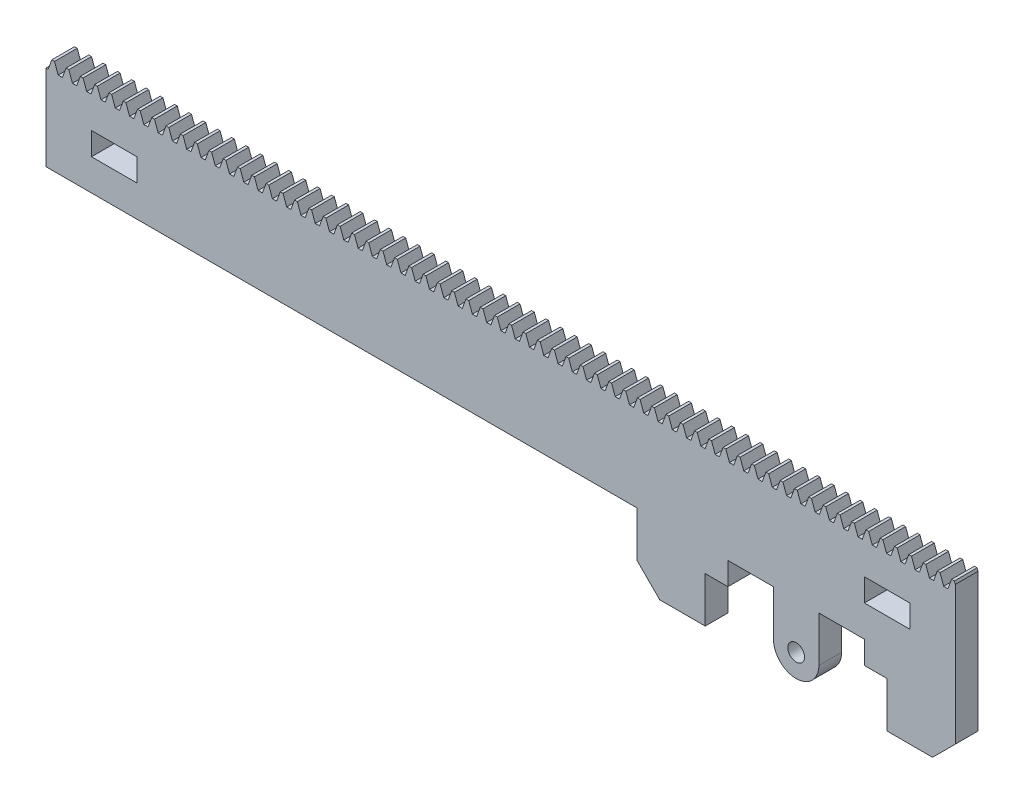
SolidWorks part; units mm, degrees
extrude "Blank" add sketch "BlankSke" against normal blind 6.35
sketch "BlankSke" plane through (0, 0, 0) normal (0, 0, 1) x (1, 0, 0)
  line L1 (0, 0) -> (254, 0)
  line L2 (0, 0) -> (0, 26.67)
  line L3 (0, 26.67) -> (254, 26.67)
  line L4 (254, 0) -> (254, 26.67)
  dimension "Length" = 254
ref_plane "Plane1" through (0, 0, 0) normal (0, 0, 1) x (1, 0, 0)
ref_plane "Plane2" through (0, 0, 0) normal (0, 1, 0) x (1, 0, 0)
ref_plane "Plane3" through (0, 0, 0) normal (1, 0, 0) x (0, 0, -1)
sketch "HoldingSke" plane through (0, 0, 0) normal (0, 1, 0) x (1, 0, 0)
  line L0 (0, 0) -> (389.1506, -326.5361)
  line L1 (-15, 0) -> (100, 0) construction
  line L2 (0, 0) -> (-2.1039, 2.3779)
  line L3 (0, 0) -> (-11.863, 4.5341)
  line L4 (0, 0) -> (3.6497, 7.8269)
  line L5 (0, 0) -> (-23.7986, -8.8762)
  line L6 (0, 0) -> (-10.5278, -7.1032)
  line L9 (-71.009, 38.7566) -> (167.673, 125.6297)
  line L10 (-76.2, 71.12) -> (-50.8, 71.12)
  line L11 (0, 0) -> (-6.35, 0)
  line L12 (-76.2, 101.6) -> (-76.1492, 101.6)
  line L13 (24.9733, 27.94) -> (52.9518, 28.4284)
  line L14 (24.9733, 27.94) -> (25.0241, 27.9398)
  line L15 (24.9733, 27.94) -> (100.4021, 29.52)
  circle A0 centre (0, 0) radius 19.05
  circle A1 centre (0, 0) radius 12.7
  circle A2 centre (0, 0) radius 12.7
  dimension "Num_teeth" = 65
  dimension "Width" = 6.35
  dimension "Length" = 254
  dimension "Pitch_height" = 25.4
sketch "TooCutSkeIll" plane through (0, 0, 0) normal (0, 0, 1) x (1, 0, 0)
  line L0 (-1.5999, 26.6366) -> (-0.6682, 24.0766)
  line L1 (-0.3817, 23.876) -> (0.3817, 23.876)
  line L2 (0.6682, 24.0766) -> (1.5999, 26.6366)
  line L3 (254, 26.67) -> (0, 26.67) construction
  line L4 (0, 0) -> (0, 64.897) construction
  line L5 (-13.208, 25.4) -> (12.954, 25.4) construction
  line L6 (0, 0) -> (254, 0) construction
  line L7 (1.1499, 25.4) -> (1.1499, 48.7463) construction
  line L8 (-1.1499, 25.4) -> (-1.1499, 48.7463) construction
  line L9 (1.6477, 26.67) -> (1.6477, 26.6954)
  line L10 (-1.6477, 26.67) -> (-1.6477, 26.6954)
  line L11 (-1.6477, 26.6954) -> (1.6477, 26.6954)
  arc A0 (0.3817, 23.876) -> (0.6682, 24.0766) centre (0.3817, 24.1808) ccw
  arc A1 (-0.6682, 24.0766) -> (-0.3817, 23.876) centre (-0.3817, 24.1808) ccw
  arc A2 (1.6477, 26.67) -> (1.5999, 26.6366) centre (1.6477, 26.6192) ccw
  arc A3 (-1.5999, 26.6366) -> (-1.6477, 26.67) centre (-1.6477, 26.6192) ccw
  dimension "Addendum_plus" = 1.2954
  dimension "Pitch_height" = 25.4
  dimension "Pressure_angle" = 20
  dimension "Gap_width" = 2.2997
  dimension "Dedendum" = 1.524
extrude "ToothCutIll" [suppressed] cut sketch "TooCutSkeIll" against normal through all
sketch "TooCutSkeSim" plane through (0, 0, 0) normal (0, 0, 1) x (1, 0, 0)
  line L0 (0.5952, 23.876) -> (-0.5952, 23.876)
  line L1 (1.6213, 26.6954) -> (0.5952, 23.876)
  line L2 (0, 17.4625) -> (0, 53.467) construction
  line L3 (1.6213, 26.6954) -> (-1.6213, 26.6954)
  line L6 (-1.6213, 26.6954) -> (-0.5952, 23.876)
  line L9 (-1.1499, 25.4) -> (1.1499, 25.4) construction
  line L10 (0, 0) -> (254, 0) construction
  line L11 (1.1499, 25.4) -> (1.1499, 53.467) construction
  line L12 (-1.1499, 25.4) -> (-1.1499, 53.467) construction
  dimension "Addendum_plus" = 1.2954
  dimension "Pitch_height" = 25.4
  dimension "Pressure_angle" = 20
  dimension "Gap_width" = 2.2997
  dimension "Dedendum" = 1.524
extrude "ToothCutSim" cut sketch "TooCutSkeSim" against normal through all
pattern_linear "TeethCuts" count 65 spacing 3.9898 along (1, 0, 0) of "ToothCutIll", "ToothCutSim"
sketch "Sketch3" plane through (0, 0, 0) normal (0, 0, 1) x (1, 0, 0)
  line L0 (0, 0) -> (254, 0) construction
  line L1 (234.95, 0) -> (254, 0)
  line L2 (234.95, -6.35) -> (234.95, -19.05)
  line L3 (234.95, -19.05) -> (254, -19.05)
  line L4 (254, 0) -> (254, -19.05)
  line L5 (254, 0) -> (254, 25.9462) construction
  line L6 (209.55, -6.35) -> (209.55, 0) construction
  line L7 (234.95, -6.35) -> (228.6, -6.35)
  line L8 (215.9, 0) -> (203.2, 0)
  line L9 (234.95, 0) -> (228.6, 0)
  line L10 (228.6, -6.35) -> (228.6, 0)
  line L11 (215.9, 0) -> (215.9, -6.35)
  line L12 (215.9, -6.35) -> (203.2, -6.35)
  line L13 (203.2, 0) -> (203.2, -6.35)
  line L14 (190.5, -6.35) -> (190.5, 0)
  line L15 (184.15, 0) -> (190.5, 0)
  line L16 (184.15, -6.35) -> (190.5, -6.35)
  line L17 (165.1, 0) -> (165.1, -19.05)
  line L18 (184.15, -19.05) -> (165.1, -19.05)
  line L19 (184.15, -6.35) -> (184.15, -19.05)
  line L20 (184.15, 0) -> (165.1, 0)
  dimension "D1" = 19.05
  dimension "D2" = 0
  dimension "D3" = 19.05
  dimension "D4" = 6.35
  dimension "D5" = 6.35
  dimension "D6" = 6.35
  dimension "D7" = 12.7
  dimension "D8" = 12.7
extrude "Boss-Extrude2" add sketch "Sketch3" against normal up to surface (6.35 mm away) up to face at (127.1733, 25.0804, -6.35)
sketch "Sketch4" plane through (0, 0, 0) normal (0, 0, 1) x (1, 0, 0)
  line L0 (209.55, -6.35) -> (209.55, -12.5878) construction
  line L1 (203.2, -6.35) -> (215.9, -6.35) construction
  line L2 (215.9, 0) -> (228.6, 0) construction
  line L3 (215.9, -12.7) -> (215.9, -6.35)
  line L4 (215.9, -6.35) -> (203.2, -6.35)
  line L5 (203.2, -6.35) -> (203.2, -12.7)
  circle A0 centre (209.55, -12.7) radius 2.3495
  arc A1 (203.2, -12.7) -> (215.9, -12.7) centre (209.55, -12.7) ccw
  dimension "D1" = 4.699
  dimension "D2" = 12.7
extrude "Boss-Extrude3" add sketch "Sketch4" against normal up to surface (6.35 mm away) up to face at (130.7232, 23.3872, -6.35)
chamfer "Chamfer1" distance 6.35 angle 45 2 edges at (165.1, -19.05, -3.175) (254, -19.05, -3.175)
sketch "Sketch6" plane through (0, 0, -6.35) normal (0, 0, -1) x (-1, 0, 0)
  line L0 (0, 11.938) -> (-254, 11.938) construction
  line L1 (0, 23.876) -> (0, 0) construction
  line L2 (-254, -12.7) -> (-254, 25.9462) construction
  line L4 (-25.4, 8.763) -> (-12.7, 8.763)
  line L5 (-25.4, 8.763) -> (-25.4, 15.113)
  line L6 (-25.4, 15.113) -> (-12.7, 15.113)
  line L7 (-12.7, 8.763) -> (-12.7, 15.113)
  line L8 (-25.4, 8.763) -> (-12.7, 15.113) construction
  line L9 (-25.4, 15.113) -> (-12.7, 8.763) construction
  point P6 (-19.05, 11.938)
  dimension "D1" = 12.7
  dimension "D2" = 6.35
  dimension "D3" = 12.7
extrude "Cut-Extrude2" cut sketch "Sketch6" against normal through all
sketch "Sketch8" plane through (0, 0, -6.35) normal (0, 0, -1) x (-1, 0, 0)
  line L0 (0, 11.938) -> (-254, 11.938) construction
  line L1 (0, 23.876) -> (0, 0) construction
  line L2 (-254, -12.7) -> (-254, 25.9462) construction
  line L4 (-228.6, 8.763) -> (-241.3, 8.763)
  line L5 (-228.6, 8.763) -> (-228.6, 15.113)
  line L6 (-228.6, 15.113) -> (-241.3, 15.113)
  line L7 (-241.3, 8.763) -> (-241.3, 15.113)
  line L8 (-228.6, 8.763) -> (-241.3, 15.113) construction
  line L9 (-228.6, 15.113) -> (-241.3, 8.763) construction
  point P6 (-234.95, 11.938)
  dimension "D1" = 12.7
  dimension "D2" = 6.35
  dimension "D3" = 12.7
extrude "Cut-Extrude3" cut sketch "Sketch8" against normal through all
equation "' \"Pitch@HoldingSke\" = 4"
equation "' \"Num_teeth@HoldingSke\" = 12"
equation "' \"Ap@HoldingSke\" =  20"
equation "' \"Ap@HoldingSke\" = 20"
equation "' \"Width@HoldingSke\" = 0.25"
equation "' \"Show_teeth@HoldingSke\" = 500"
equation "' \"Backlash@HoldingSke\" = 0.009"
equation "' \"Addendum_fac@HoldingSke\" = 1.0"
equation "' \"Dedendum_fac@HoldingSke\" = 1.25"
equation "' \"Dedendum_add@HoldingSke\" = 0.00005"
equation "' \"Clearance_fac@HoldingSke\" = 0.25"
equation "' \"Pitch_height@HoldingSke\" = 1"
equation "' \"Length@HoldingSke\" = 4.71"
equation "\"MPH@HoldingSke\" = \"Dedendum_fac@HoldingSke\" / \"Pitch@HoldingSke\" + 2 * \"Dedendum_add@HoldingSke\" + 0.002"
equation "\"MPH@HoldingSke\" = ((sgn( \"MPH@HoldingSke\" - \"Pitch_height@HoldingSke\")+1)*( \"MPH@HoldingSke\" - \"Pitch_height@HoldingSke\"))/2 + \"Pitch_height@HoldingSke\""
equation "\"Blank_height@BlankSke\" = \"Pitch_height@HoldingSke\" + \"Addendum_fac@HoldingSke\"  / \"Pitch@HoldingSke\" "
equation "\"Length@BlankSke\" =  \"Length@HoldingSke\""
equation "\"Face_width@Blank\" = \"Width@HoldingSke\""
equation "\"Pressure_angle@TooCutSkeIll\" = \"Ap@HoldingSke\""
equation "\"Addendum_plus@TooCutSkeIll\" =  \"Addendum_fac@HoldingSke\"  / \"Pitch@HoldingSke\" + 0.001"
equation "\"Dedendum@TooCutSkeIll\" = \"Dedendum_fac@HoldingSke\"  / \"Pitch@HoldingSke\""
equation "\"Pitch_height@TooCutSkeIll\" =  \"MPH@HoldingSke\""
equation "\"Gap_width@TooCutSkeIll\" = 3.14159265 / 2 / \"Pitch@HoldingSke\" + 6 * \"Backlash@HoldingSke\""
equation "\"Pressure_angle@TooCutSkeSim\" = \"Ap@HoldingSke\""
equation "\"Addendum_plus@TooCutSkeSim\" =  \"Addendum_fac@HoldingSke\"  / \"Pitch@HoldingSke\" + 0.001"
equation "\"Dedendum@TooCutSkeSim\" = \"Dedendum_fac@HoldingSke\"  / \"Pitch@HoldingSke\""
equation "\"Pitch_height@TooCutSkeSim\" =  \"MPH@HoldingSke\""
equation "\"Gap_width@TooCutSkeSim\" = 3.14159265 / 2 / \"Pitch@HoldingSke\" + 6 * \"Backlash@HoldingSke\""
equation "\"Root_fillet@TooCutSkeIll\" = \"Clearance_fac@HoldingSke\" / \"Pitch@HoldingSke\" + \"Dedendum_add@HoldingSke\""
equation "\"Break_rad@TooCutSkeIll\" = 0.02 / \"Pitch@HoldingSke\" * 2"
equation "\"Linear_pitch@TeethCuts\" = 3.14159265 / \"Pitch@HoldingSke\""
equation "\"Num_teeth@HoldingSke\" = int( ( \"Length@HoldingSke\" + 0 ) / (3.14159265 / \"Pitch@HoldingSke\")) + 0.9999  + 1"
equation " \"Num_teeth@TeethCuts\" = int( \"Show_teeth@HoldingSke\" ) + 1"
equation " \"Num_teeth@TeethCuts\" = ((sgn( \"Num_teeth@TeethCuts\" - \"Num_teeth@HoldingSke\" )-1)*( \"Num_teeth@TeethCuts\" - \"Num_teeth@HoldingSke\" ))/-2+ \"Num_teeth@HoldingSke\""
equation " \"Num_teeth@TeethCuts\" = ((sgn( \"Num_teeth@TeethCuts\" - 2.0)+1)*( \"Num_teeth@TeethCuts\" - 2.0))/2 +2.0"
